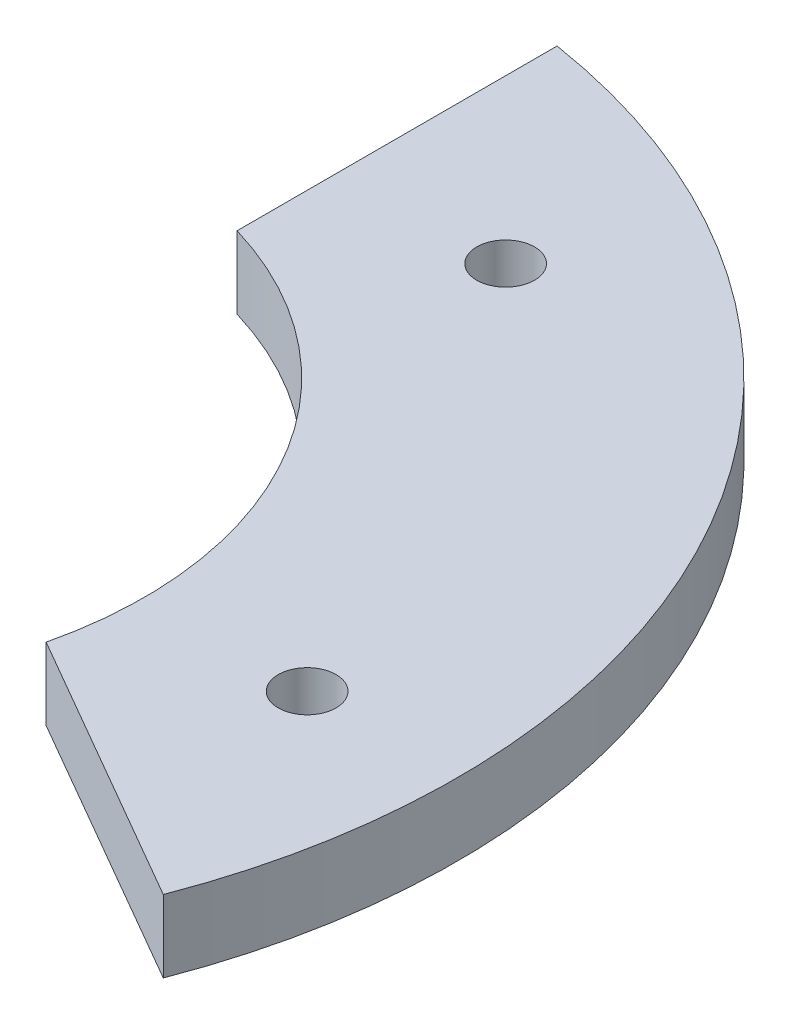
SolidWorks part; units mm, degrees
material "Balsa"
ref_plane "Front Plane" through (0, 0, 0) normal (0, 0, 1) x (1, 0, 0)
ref_plane "Top Plane" through (0, 0, 0) normal (0, 1, 0) x (1, 0, 0)
ref_plane "Right Plane" through (0, 0, 0) normal (1, 0, 0) x (0, 0, -1)
sketch "Sketch1" plane through (0, 0, 0) normal (0, 1, 0) x (1, 0, 0)
  line L0 (-38.3, 0) -> (38.3, 0) construction
  line L1 (0, 38.3) -> (0, -38.3) construction
  circle A0 centre (0, 0) radius 38.3
  circle A1 centre (30, 0) radius 1.6
  circle A2 centre (0, 0) radius 21
  circle A3 centre (15, -25.9808) radius 1.6
  circle A4 centre (-15, -25.9808) radius 1.6
  circle A5 centre (-30, 0) radius 1.6
  circle A6 centre (-15, 25.9808) radius 1.6
  circle A7 centre (15, 25.9808) radius 1.6
  point P23 (0, 0)
  dimension "D1" = 42
  dimension "D2" = 76.6
  dimension "D3" = 3.2
  dimension "D4" = 30
  dimension "D5" = 6
extrude "Boss-Extrude1" add sketch "Sketch1" along normal blind 4
sketch "Sketch2" plane through (0, 4, 0) normal (0, 1, 0) x (1, 0, 0)
  line L0 (0, 0) -> (0, 45.284) construction
  line L1 (0, 0) -> (52.3716, -30.2368) construction
  line L2 (6, 50.2763) -> (6, 14.2975)
  line L3 (15.382, -1.9526) -> (46.5406, -19.942)
  arc A0 (15.382, -1.9526) -> (6, 14.2975) centre (0, 0) ccw
  arc A2 (6, 50.2763) -> (46.5406, -19.942) centre (0, 0) ccw
  dimension "D1" = 120
  dimension "D2" = 6
  dimension "D3" = 6
extrude "Cut-Extrude1" cut sketch "Sketch2" against normal blind 10 contours L2 A0 L3 A2
